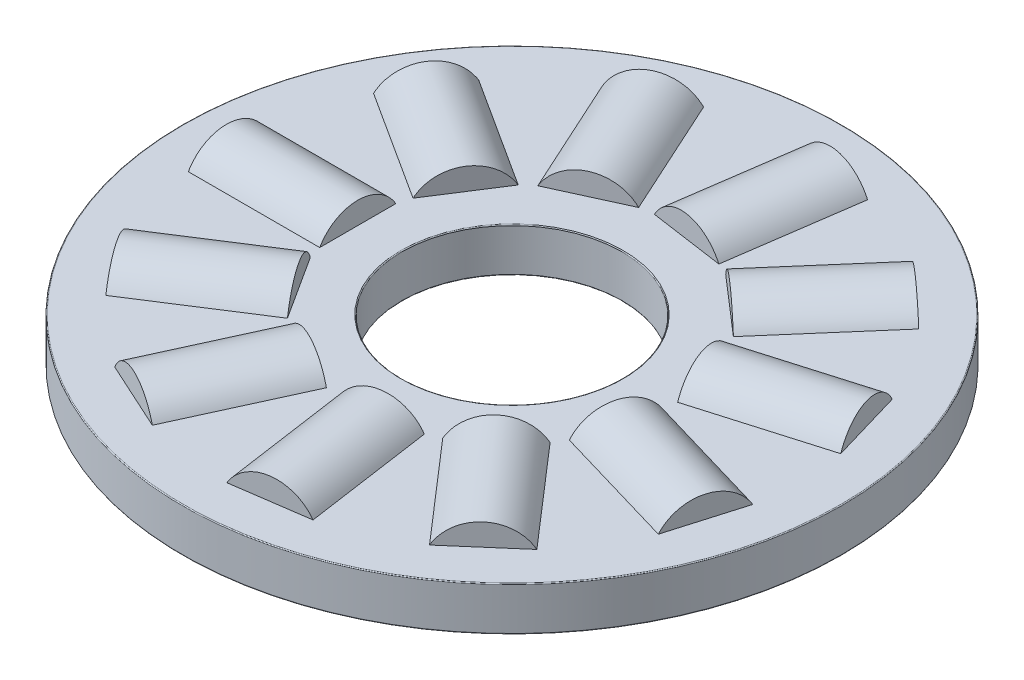
SolidWorks part; units mm, degrees
ref_plane "Front Plane" through (0, 0, 0) normal (0, 0, 1) x (1, 0, 0)
ref_plane "Top Plane" through (0, 0, 0) normal (0, 1, 0) x (1, 0, 0)
ref_plane "Right Plane" through (0, 0, 0) normal (1, 0, 0) x (0, 0, -1)
sketch "Sketch1" plane through (0, 0, 0) normal (0, 1, 0) x (1, 0, 0)
  line L0 (0, 7.5) -> (0, -7.5) construction
  circle A0 centre (0, 0) radius 7.5 construction
  circle A1 centre (0, 0) radius 2.51 construction
  circle A2 centre (0, 0) radius 9 construction
  point P6 (5.5, 0)
  dimension "ID" = 5.02
  dimension "OD" = 15
  dimension "For Shaft Diameter" = 18
  dimension "Number of Rollers" = 11
sketch "Sketch2" plane through (0, 0, 0) normal (0, 0, 1) x (1, 0, 0)
  line L0 (0, 0.5) -> (0, -0.5) construction
  line L1 (-7.5, 0.5) -> (7.5, 0.5) construction
  line L2 (-7.5, 0.5) -> (-7.5, -0.5) construction
  line L3 (-7.5, -0.5) -> (7.5, -0.5) construction
  line L4 (7.5, 0.5) -> (7.5, -0.5) construction
  line L5 (3.51, 1) -> (6.5, 1) construction
  line L6 (3.51, 1) -> (3.51, -1) construction
  line L7 (3.51, -1) -> (6.5, -1) construction
  line L8 (-2.51, 0.5) -> (-2.51, -0.5) construction
  line L9 (2.51, 0.5) -> (2.51, -0.5) construction
  line L10 (6.5, 1) -> (6.5, -1) construction
  line L11 (-6.5, 1) -> (-3.51, 1) construction
  line L12 (-6.5, 1) -> (-6.5, -1) construction
  line L13 (-6.5, -1) -> (-3.51, -1) construction
  line L14 (-3.51, 1) -> (-3.51, -1) construction
  line L15 (7.5, 0) -> (-7.5, 0) construction
  point P4 (7.5, 0)
  point P5 (-7.5, 0)
  point P12 (-2.51, 0)
  point P13 (2.51, 0)
  point P26 (3.51, 0)
  dimension "Washer Thickness" = 1
  dimension "Thickness" = 2
  dimension "Ci | Roller ID" = 7.02
  dimension "Ce | Roller OD" = 13
sketch "Sketch3" plane through (0, 0, 0) normal (0, 0, 1) x (1, 0, 0)
  line L1 (-7.48, 0.5) -> (-2.53, 0.5)
  line L2 (-7.5, 0.48) -> (-7.5, -0.48)
  line L3 (-7.48, -0.5) -> (-2.53, -0.5)
  line L4 (-2.51, 0.48) -> (-2.51, -0.48)
  arc A0 (-7.5, -0.48) -> (-7.48, -0.5) centre (-7.48, -0.48) ccw
  arc A1 (-7.48, 0.5) -> (-7.5, 0.48) centre (-7.48, 0.48) ccw
  arc A2 (-2.53, -0.5) -> (-2.51, -0.48) centre (-2.53, -0.48) ccw
  arc A3 (-2.53, 0.5) -> (-2.51, 0.48) centre (-2.53, 0.48) cw
  point P10 (-7.5, 0.5)
  point P13 (-2.51, -0.5)
  dimension "D1" = 0.02
revolve "Revolve1" add sketch "Sketch3" angle 360 about L0
sketch "Sketch4" plane through (0, 0, 0) normal (0, 0, 1) x (1, 0, 0)
  line L0 (-3.51, 1) -> (-3.51, -1) construction
  line L1 (-6.5, 1) -> (-3.51, 1)
  line L2 (-6.5, 1) -> (-6.5, 0)
  line L3 (-6.5, 0) -> (-3.51, 0)
  line L4 (-3.51, 1) -> (-3.51, 0)
revolve "Cut-Revolve1" cut sketch "Sketch4" angle 360 about L3
sketch "Sketch5" plane through (0, 0, 0) normal (0, 0, 1) x (1, 0, 0)
  line L0 (-3.51, 1) -> (-3.51, -1) construction
  line L1 (-3.51, 0) -> (-6.5, 0)
  line L2 (-3.51, 0) -> (-3.51, 1)
  line L3 (-3.51, 1) -> (-6.5, 1)
  line L4 (-6.5, 0) -> (-6.5, 1)
revolve "Revolve2" add sketch "Sketch5" angle 360 about L1
pattern_circular "CirPattern2" count 11 over 360 about axis through (0, 0.5, 0) along (0, -1, 0) of "Cut-Revolve1"
pattern_circular "CirPattern3" count 11 over 360 about axis through (0, 0.5, 0) along (0, -1, 0) reverse direction yes of bodies 106
ref_axis "Axis1" through (0, -0.48, 0) along (0, 1, 0)
ref_plane "Plane1" through (0, 1, 0) normal (0, 1, 0) x (1, 0, 0)
ref_plane "Plane2" through (0, -1, 0) normal (0, -1, 0) x (-1, 0, 0)
equation "\"D1@CirPattern2\"=\"Number of Rollers@Sketch1\""
equation "\"D1@CirPattern3\"=\"Number of Rollers@Sketch1\""
equation "\"Number of Rollers@Sketch1\" = int ( \"OD@Sketch1\" * .8 ) "
equation "\"Washer Thickness@Sketch2\" = \"Thickness@Sketch2\" / 2"
equation "\"Ci | Roller ID@Sketch2\" = \"ID@Sketch1\" + \"Thickness@Sketch2\""
equation "\"Ce | Roller OD@Sketch2\" = \"OD@Sketch1\" - \"Thickness@Sketch2\""
